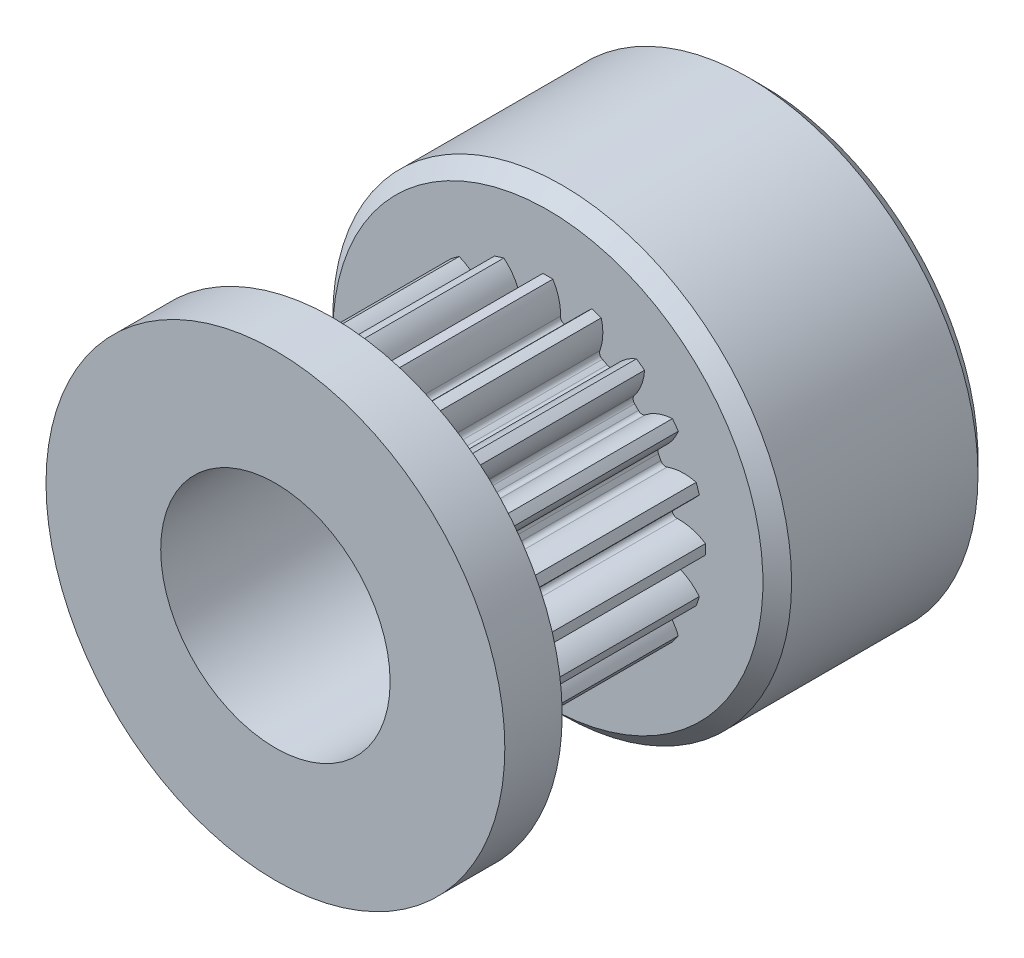
SolidWorks part; units mm, degrees
material "ABS"
ref_plane "Plane1" through (0, 0, 0) normal (0, 0, 1) x (1, 0, 0)
ref_plane "Plane2" through (0, 0, 0) normal (0, 1, 0) x (1, 0, 0)
ref_plane "Plane3" through (0, 0, 0) normal (1, 0, 0) x (0, 0, -1)
sketch "Esquisse1" plane through (0, 0, 0) normal (0, 0, 1) x (1, 0, 0)
  circle A0 centre (0, 0) radius 1.15
  dimension "D1" = 2.3
extrude "Base-Extrusion" add sketch "Esquisse1" along normal blind 2.5
sketch "Parametres" plane through (0, 0, 2.5) normal (0, 0, 1) x (1, 0, 0)
  line L0 (-33.4711, 41.7411) -> (-13.4711, 41.7411)
  line L1 (-33.4711, 34.0759) -> (-32.9711, 34.0759)
  line L2 (-33.4711, 23.0892) -> (-13.4711, 23.0892)
  line L3 (-33.4711, -2.6579) -> (-33.1221, -2.6579)
  line L4 (-38.9094, -12.5583) -> (-35.7678, -12.5583)
  line L5 (-48.8826, -19.2556) -> (-43.8826, -19.2556)
  line L6 (-48.8826, -29.9283) -> (-43.3826, -29.9283)
  line L7 (-48.8826, -38.2322) -> (-44.5076, -38.2322)
  line L8 (-48.8826, -45.1309) -> (-44.1841, -45.1309)
  line L9 (-48.8826, -60.7647) -> (-48.0972, -60.7647)
  line L10 (-48.8826, -76.1039) -> (-48.0045, -76.1039)
  line L11 (-48.8826, -88.0795) -> (-48.3359, -88.0795)
  line L12 (-48.8826, -98.8973) -> (-48.5351, -98.8973)
  line L13 (16.9123, -61.9871) -> (25.9123, -61.9871)
  line L14 (18.5152, -81.0212) -> (29.2231, -81.0212)
  line L15 (18.5152, -96.0481) -> (22.1346, -96.0481)
  line L16 (-33.4711, 13.8609) -> (-26.8711, 13.8609)
sketch "Esquisse3" plane through (0, 0, 0) normal (0, 0, 1) x (1, 0, 0)
  line L0 (0, 0) -> (0, 29.3764) construction
  line L1 (-0.6844, 4.3211) -> (0, 0)
  line L2 (0, 0) -> (0.6844, 4.3211)
  line L3 (0, 0) -> (0.4384, 4.678) construction
  line L4 (0, 0) -> (0.1737, 5.4973) construction
  line L5 (0, 0) -> (0.3923, 4.9846) construction
  arc A0 (0.1737, 5.4973) -> (0.4268, 4.3541) centre (-1.2732, 4.5773) cw
  arc A1 (-0.1737, 5.4973) -> (-0.4268, 4.3541) centre (1.2732, 4.5773) ccw
  arc A2 (0.6844, 4.3211) -> (0.4268, 4.3541) centre (0, 0) ccw
  arc A3 (-0.6844, 4.3211) -> (-0.4268, 4.3541) centre (0, 0) cw
  arc A4 (0.1737, 5.4973) -> (-0.1737, 5.4973) centre (0, 0) ccw
  dimension "D4" = 18
  dimension "D5" = 4.6985
  dimension "D6" = 5
  dimension "D1" = 5.5
  dimension "D2" = 5.354
  dimension "D3" = 4.5
  dimension "D7" = 1.81
  dimension "D8" = 4.375
extrude "Boss.-Extru.1" add sketch "Esquisse3" along normal blind 7.5
fillet "Congé1" radius 0.175 2 edges at (0.4268, 4.3541, 3.75) (-0.4268, 4.3541, 3.75)
ref_axis "Axe1" through (0, 0, 57.5) along (0, 0, -1)
pattern_circular "Répétition circulaire4" count 20 every 18 about axis through (0, 0, 57.5) along (0, 0, -1) of "Boss.-Extru.1", "Congé1"
sketch "Sketch2" plane through (0, 0, 7.5) normal (0, 0, 1) x (1, 0, 0)
  circle A0 centre (0, 0) radius 8
  dimension "D1" = 16
extrude "Boss-Extrude1" add sketch "Sketch2" along normal blind 2 contours A0
sketch "Sketch3" plane through (0, 0, 0) normal (0, 0, -1) x (-1, 0, 0)
  circle A0 centre (0, 0) radius 8
extrude "Boss-Extrude2" add sketch "Sketch3" along normal blind 7.5
sketch "Sketch4" plane through (0, 0, -7.5) normal (0, 0, -1) x (-1, 0, 0)
  circle A0 centre (0, 0) radius 4
  dimension "D1" = 8
extrude "Cut-Extrude1" cut sketch "Sketch4" against normal through all
chamfer "Chamfer1" distance 0.5 angle 45 2 edges at (-8, 0, 0) (-8, 0, -7.5)
sketch "Sketch6" plane through (0, 0, 0) normal (0, 1, 0) x (1, 0, 0)
  circle A0 centre (0, 3.75) radius 2
  dimension "D1" = 4
  dimension "D2" = 3.75
extrude "Cut-Extrude2" cut sketch "Sketch6" against normal through all
sketch "Sketch7" plane through (0, 0, 0) normal (1, 0, 0) x (0, 0, -1)
  circle A0 centre (3.75, 0) radius 2
  dimension "D1" = 4
  dimension "D2" = 3.75
extrude "Cut-Extrude3" cut sketch "Sketch7" against normal through all
equation "\"PI@Parametres\" = 3.141592654"
equation "\"Alpha_rad@Parametres\" = \"Alpha@Parametres\"*\"PI@Parametres\"/180"
equation "\"R@Parametres\" = \"Z@Parametres\"*\"m@Parametres\"/2"
equation "\"RT@Parametres\" = \"R@Parametres\"+\"m@Parametres\""
equation "\"RP@Parametres\" = \"R@Parametres\"-1.25*\"m@Parametres\""
equation "\"Rb@Parametres\" = \"R@Parametres\"*cos(\"Alpha_rad@Parametres\")"
equation "\"E@Parametres\" = \"PI@Parametres\"*\"R@Parametres\"/\"Z@Parametres\""
equation "\"Eb@Parametres\" = \"Rb@Parametres\"*((\"PI@Parametres\"*\"m@Parametres\"/(2*\"R@Parametres\"))+2*(tan(\"Alpha_rad@Parametres\")-\"Alpha_rad@Parametres\"))"
equation "\"As@Parametres\" = atn(sqr(\"RT@Parametres\"*\"RT@Parametres\"-\"Rb@Parametres\"*\"Rb@Parametres\")/\"Rb@Parametres\")"
equation "\"Et@Parametres\" = \"RT@Parametres\"*((\"E@Parametres\"/\"R@Parametres\")+2*(tan(\"Alpha_rad@Parametres\")-\"Alpha_rad@Parametres\"-tan(\"As@Parametres\")+\"As@Parametres\"))"
equation "\"Ap@Parametres\" = (\"E@Parametres\"/\"R@Parametres\")*180/\"PI@Parametres\""
equation "\"Ab@Parametres\" = (\"Eb@Parametres\"/\"Rb@Parametres\")*180/\"PI@Parametres\""
equation "\"At@Parametres\" = (\"Et@Parametres\"/\"RT@Parametres\")*180/\"PI@Parametres\""
equation "\"D7@Esquisse3\" = \"At@Parametres\"/2"
equation "\"D3@Esquisse3\"=\"Ap@Parametres\"/2"
equation "\"D2@Esquisse3\"=\"Ab@Parametres\"/2"
equation "\"D5@Esquisse3\"=\"Rb@Parametres\""
equation "\"D6@Esquisse3\"=\"R@Parametres\""
equation "\"D1@Esquisse3\"=\"RT@Parametres\""
equation "\"D4@Esquisse3\" = \"Ap@Parametres\"*2"
equation "\"D1@Congé1\" = 0.35*\"m@Parametres\""
equation "\"D2@Répétition circulaire4\" = \"Ap@Parametres\"*2"
equation "\"D1@Répétition circulaire4\" = \"Z@Parametres\""
equation "\"D8@Esquisse3\" = \"RP@Parametres\""
